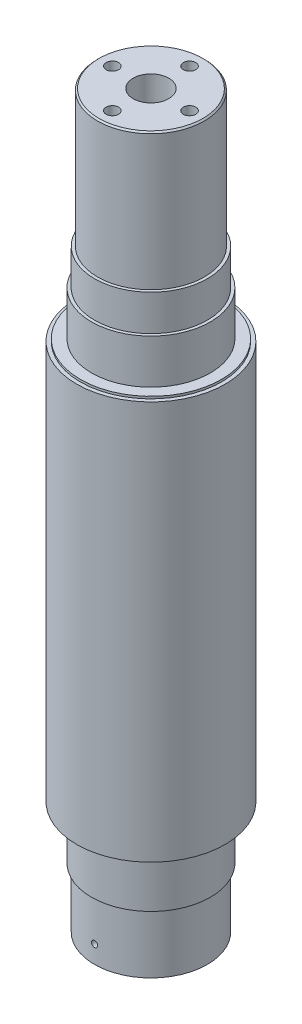
SolidWorks part; units mm, degrees
material "Stainless Steel (ferritic)"
ref_plane "Front" through (0, 0, 0) normal (0, 0, 1) x (1, 0, 0)
ref_plane "Top" through (0, 0, 0) normal (0, 1, 0) x (1, 0, 0)
ref_plane "Right" through (0, 0, 0) normal (1, 0, 0) x (0, 0, -1)
sketch "Sketch1" plane through (0, 0, 0) normal (0, 1, 0) x (1, 0, 0)
  circle A0 centre (0, 0) radius 25
  dimension "D1" = 50
extrude "Boss-Extrude1" add sketch "Sketch1" along normal blind 95 and the other way blind 105
sketch "Sketch2" plane through (0, 95, 0) normal (0, 1, 0) x (1, 0, 0)
  circle A0 centre (0, 0) radius 18
  dimension "D1" = 36
extrude "Boss-Extrude2" add sketch "Sketch2" along normal blind 46
ref_plane "Plane1" through (0, 0, -15) normal (0, 0, 1) x (1, 0, 0)
sketch "Sketch8" plane through (0, 0, -15) normal (0, 0, 1) x (1, 0, 0)
  line L0 (0, 122) -> (0, 103) construction
  line L1 (3, 122) -> (3, 103)
  line L2 (-3, 122) -> (-3, 103)
  line L4 (25, 95) -> (-25, 95) construction
  arc A0 (3, 122) -> (-3, 122) centre (0, 122) ccw
  arc A1 (-3, 103) -> (3, 103) centre (0, 103) ccw
  point P2 (0, 112.5)
  dimension "D2" = 3
  dimension "D1" = 17.5
  dimension "D3" = 9.5
extrude "Cut-Extrude1" cut sketch "Sketch8" against normal blind 10
chamfer "Chamfer1" distance 0.5 angle 45 1 edges at (0, 141, 18)
sketch "Sketch9" plane through (0, -105, 0) normal (0, -1, 0) x (1, 0, 0)
  circle A0 centre (0, 0) radius 10
  dimension "D1" = 20
extrude "Cut-Extrude2" cut sketch "Sketch9" against normal blind 30 draft 8
sketch "Sketch10" plane through (0, -105, 0) normal (0, -1, 0) x (1, 0, 0)
  circle A0 centre (0, 0) radius 6.5
  dimension "D1" = 13
extrude "Cut-Extrude3" cut sketch "Sketch10" against normal blind 50
sketch "Sketch11" plane through (0, 141, 0) normal (0, 1, 0) x (1, 0, 0)
  circle A0 centre (0, 0) radius 6
  dimension "D1" = 12
extrude "Cut-Extrude4" cut sketch "Sketch11" against normal through all
hole_wizard "M5x0.8 Tapped Hole1" positions "Sketch13" profile "Sketch15" tap size "M5x0.8" standard "ANSI Metric"
sketch "Sketch13" plane through (0, 141, 0) normal (0, 1, 0) x (1, 0, 0)
  point P0 (0, 13)
  dimension "D1" = 13
sketch "Sketch15" plane through (0, 141, -13) normal (1, 0, 0) x (0, 0, 1)
  line L0 (0, 0) -> (0, 12)
  line L1 (0, 12) -> (2.1, 10.7382)
  line L2 (2.1, 10.7382) -> (2.1, 0)
  line L5 (2.1, 0) -> (0, 0)
  line L10 (0, 12) -> (-2.1, 10.7382) construction
  line L11 (0, -6.35) -> (0, 107.95) construction
  dimension "Tap Drill Dia." = 4.2
  dimension "Tap Drill Depth" = 12
  dimension "Drill Angle" = 118
cosmetic thread "Hole Thread1" parameters "D1"=10, "D2"=5
pattern_circular "CirPattern1" count 4 over 360 about axis through (0, -105, 0) along (0, 1, 0) of "M5x0.8 Tapped Hole1" reverse direction yes
cosmetic thread "Hole Thread2" parameters "D1"=10, "D2"=5
cosmetic thread "Hole Thread3" parameters "D1"=10, "D2"=5
cosmetic thread "Hole Thread4" parameters "D1"=10, "D2"=5
hole_wizard "M2.5x0.45 Tapped Hole1" positions "Sketch19" profile "Sketch20" tap size "M2.5x0.45" standard "ANSI Metric"
sketch "Sketch19" plane through (0, -105, 0) normal (0, -1, 0) x (-1, 0, 0)
  point P0 (-12.2, 0)
  dimension "D1" = 12.2
sketch "Sketch20" plane through (12.2, -105, 0) normal (1, 0, 0) x (0, 0, -1)
  line L0 (0, 0) -> (0, 9.35)
  line L1 (0, 9.35) -> (1.025, 8.7341)
  line L2 (1.025, 8.7341) -> (1.025, 0)
  line L5 (1.025, 0) -> (0, 0)
  line L10 (0, 9.35) -> (-1.025, 8.7341) construction
  line L11 (0, -6.35) -> (0, 107.95) construction
  dimension "Tap Drill Dia." = 2.05
  dimension "Tap Drill Depth" = 9.35
  dimension "Drill Angle" = 118
cosmetic thread "Hole Thread7" parameters "D1"=8, "D2"=2.5
mirror "Mirror2" about plane through (0, 0, 0) normal (1, 0, 0) of "M2.5x0.45 Tapped Hole1"
cosmetic thread "Hole Thread8" parameters "D1"=8, "D2"=2.5
sketch "Sketch21" plane through (0, -1, 0) normal (0, 1, 0) x (1, 0, 0)
  circle A0 centre (0, 0) radius 20
  circle A1 centre (0, 0) radius 25
  dimension "D1" = 40
  dimension "D2" = 50
extrude "Cut-Extrude6" cut sketch "Sketch21" along normal blind 27 from offset 69
extrude "Cut-Extrude7" cut sketch "Sketch21<2>" against normal blind 39 from offset 66 offset against normal yes
sketch "Sketch21<2>" plane through (0, -1, 0) normal (0, 1, 0) x (1, 0, 0) same geometry as "Sketch21"
sketch "Sketch23" plane through (0, 95, 0) normal (0, 1, 0) x (1, 0, 0)
  circle A0 centre (0, 0) radius 25
  circle A1 centre (0, 0) radius 23.75
  dimension "D1" = 47.5
  dimension "D2" = 50
extrude "Cut-Extrude8" cut sketch "Sketch23" against normal blind 0.75 from offset 27 offset against normal yes
sketch "Sketch24" plane through (0, -105, 0) normal (0, -1, 0) x (1, 0, 0)
  circle A0 centre (0, 0) radius 19
  circle A1 centre (0, 0) radius 20
  dimension "D1" = 38
  dimension "D2" = 40
extrude "Cut-Extrude9" cut sketch "Sketch24" against normal blind 20.1
hole_wizard "M2.5x0.45 Tapped Hole2" positions "3DSketch1" profile "Sketch22" tap size "M2.5x0.45" standard "ANSI Metric"
sketch3d "3DSketch1"
  point P0 (0, -99, -19)
  point P2 (0, -99, 19)
  dimension "D1" = 6
  dimension "D2" = 6
sketch "Sketch22" plane through (0, -99, -19) normal (1, 0, 0) x (0, 1, 0)
  line L0 (0, 0) -> (0, 5.6159)
  line L1 (0, 5.6159) -> (1.025, 5)
  line L2 (1.025, 5) -> (1.025, 0)
  line L5 (1.025, 0) -> (0, 0)
  line L10 (0, 5.6159) -> (-1.025, 5) construction
  line L11 (0, -6.35) -> (0, 107.95) construction
  dimension "Tap Drill Dia." = 2.05
  dimension "Tap Drill Depth" = 5
  dimension "Drill Angle" = 118
cosmetic thread "Hole Thread9" parameters "D1"=5, "D2"=2.5
cosmetic thread "Hole Thread10" parameters "D1"=5, "D2"=2.5
sketch "Sketch25" plane through (0, 95, 0) normal (0, 1, 0) x (1, 0, 0)
  circle A0 centre (0, 0) radius 19
  circle A1 centre (0, 0) radius 20
  dimension "D1" = 38
  dimension "D2" = 40
extrude "Cut-Extrude10" cut sketch "Sketch25" against normal blind 12.1
